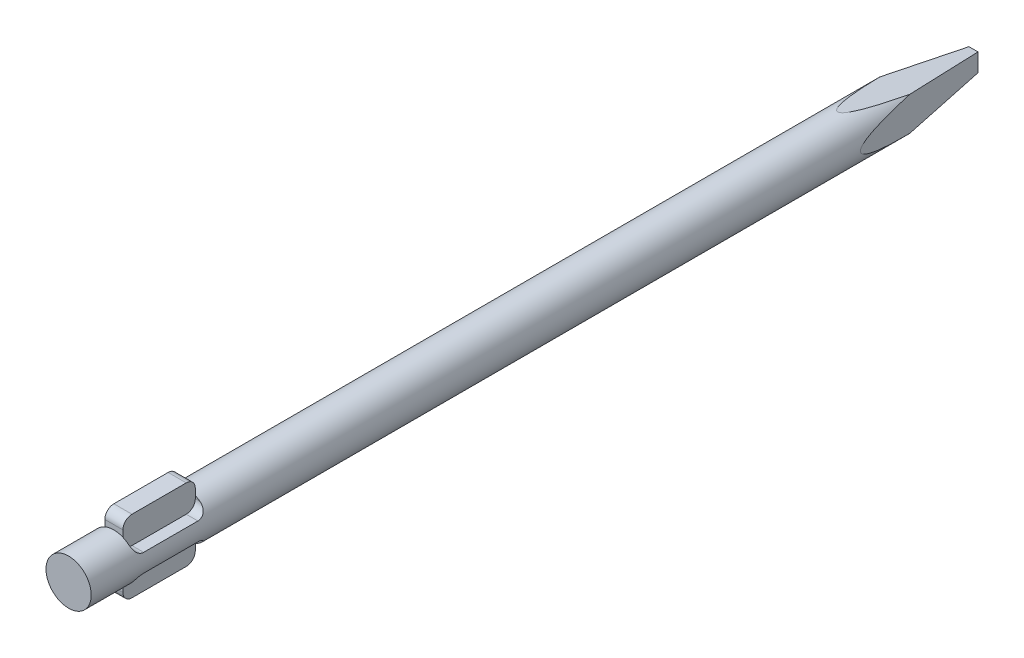
SolidWorks part; units mm, degrees
ref_plane "Front Plane" through (0, 0, 0) normal (0, 0, 1) x (1, 0, 0)
ref_plane "Top Plane" through (0, 0, 0) normal (0, 1, 0) x (1, 0, 0)
ref_plane "Right Plane" through (0, 0, 0) normal (1, 0, 0) x (0, 0, -1)
sketch "Sketch1" plane through (0, 0, 0) normal (0, 0, 1) x (1, 0, 0)
  circle A0 centre (0, 0) radius 2.5
  dimension "D1" = 5
extrude "Boss-Extrude1" add sketch "Sketch1" along normal blind 100
sketch "Sketch2" plane through (0, 0, 0) normal (1, 0, 0) x (0, 0, -1)
  line L0 (-100, 2.5) -> (-100, -2.5) construction
  line L1 (-94, 4) -> (-88, 4)
  line L2 (-95, 3) -> (-95, 2)
  line L3 (-94, 1) -> (-88, 1)
  line L4 (-87, 3) -> (-87, 2)
  line L5 (-100, 0) -> (-76.4427, 0) construction
  line L6 (-87, -3) -> (-87, -2)
  line L7 (-94, -1) -> (-88, -1)
  line L8 (-95, -3) -> (-95, -2)
  line L9 (-94, -4) -> (-88, -4)
  arc A0 (-88, 1) -> (-87, 2) centre (-88, 2) ccw
  arc A1 (-88, 4) -> (-87, 3) centre (-88, 3) cw
  arc A2 (-94, 4) -> (-95, 3) centre (-94, 3) ccw
  arc A3 (-95, 2) -> (-94, 1) centre (-94, 2) ccw
  arc A4 (-88, -4) -> (-87, -3) centre (-88, -3) ccw
  arc A5 (-88, -1) -> (-87, -2) centre (-88, -2) cw
  arc A6 (-95, -2) -> (-94, -1) centre (-94, -2) cw
  arc A7 (-94, -4) -> (-95, -3) centre (-94, -3) cw
  point P12 (-87, 1)
  point P15 (-87, 4)
  point P18 (-95, 4)
  dimension "D5" = 1
  dimension "D1" = 3
  dimension "D2" = 8
  dimension "D3" = 5
  dimension "D4" = 1
extrude "Cut-Extrude1" cut sketch "Sketch2" against normal mid plane 10
extrude "Boss-Extrude2" add sketch "Sketch2<2>" along normal mid plane 2
sketch "Sketch2<2>" plane through (0, 0, 0) normal (1, 0, 0) x (0, 0, -1) same geometry as "Sketch2"
sketch "Sketch3" plane through (0, 0, 0) normal (1, 0, 0) x (0, 0, -1)
  line L0 (0, 1) -> (0, -1)
  line L1 (0, -2.5) -> (0, 2.5) construction
  line L2 (0, -1) -> (-15, -2.5)
  line L3 (-87, -2.5) -> (0, -2.5) construction
  line L5 (0, 2.5) -> (-87, 2.5) construction
  line L6 (-15, 2.5) -> (0, 1)
  line L7 (-15, -2.5) -> (0, -2.5)
  line L8 (0, -2.5) -> (0, 2.5)
  line L9 (0, 2.5) -> (-15, 2.5)
  point P6 (0, 0)
  dimension "D1" = 2
  dimension "D2" = 15
  dimension "D3" = 15
extrude "Cut-Extrude2" cut sketch "Sketch3" against normal mid plane 12 contours L8 L9 L6 | L7 L8 L2 region at (0, -2, 5) region at (0, 2, 5)
sketch "Sketch4" plane through (0, 0, 0) normal (0, 1, 0) x (1, 0, 0)
  line L0 (-0.5, 0) -> (0.5, 0)
  line L1 (-2.2913, 0) -> (2.2913, 0) construction
  line L2 (0.5, 0) -> (2.5, -15)
  line L3 (2.5, -100) -> (2.5, 0) construction
  line L5 (-2.5, 0) -> (-2.5, -100) construction
  line L6 (-2.5, -15) -> (-0.5, 0)
  line L7 (2.5, -15) -> (2.5, 0)
  line L8 (2.5, 0) -> (-2.5, 0)
  line L9 (-2.5, 0) -> (-2.5, -15)
  point P6 (0, 0)
  dimension "D1" = 1
  dimension "D2" = 15
  dimension "D3" = 15
extrude "Cut-Extrude3" cut sketch "Sketch4" against normal mid plane 5 contours L8 L9 L6 | L7 L8 L2 region at (1.8333, 0, 5) region at (-1.8333, 0, 5)
